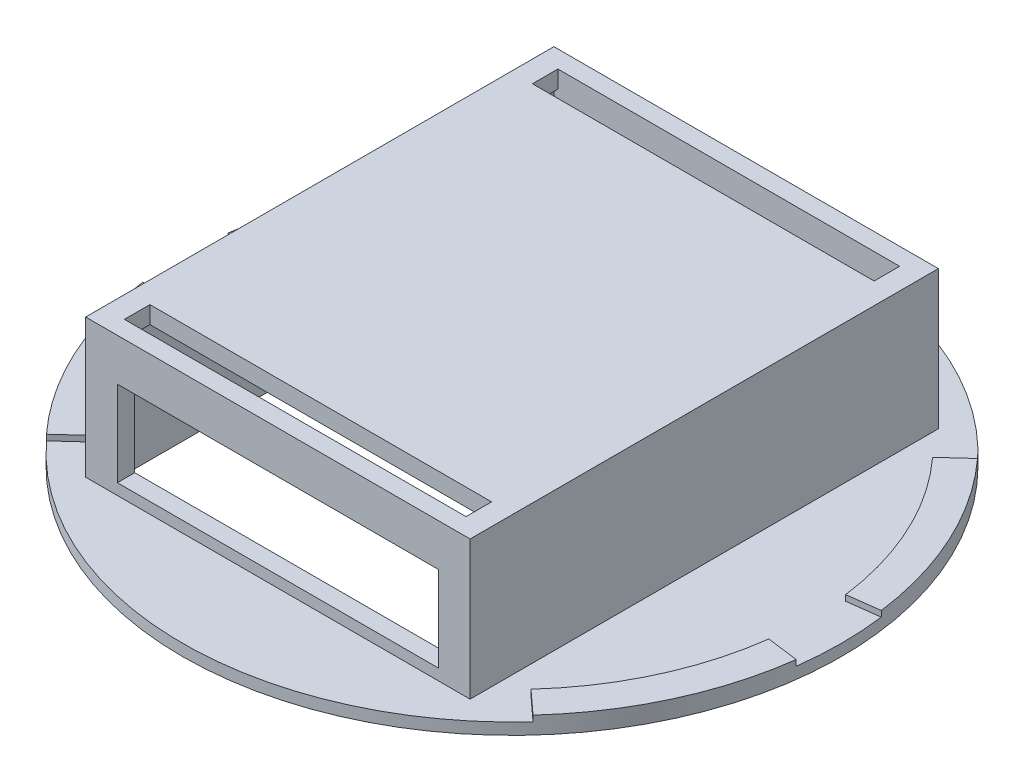
SolidWorks part; units mm, degrees
ref_plane "Front Plane" through (0, 0, 0) normal (0, 0, 1) x (1, 0, 0)
ref_plane "Top Plane" through (0, 0, 0) normal (0, 1, 0) x (1, 0, 0)
ref_plane "Right Plane" through (0, 0, 0) normal (1, 0, 0) x (0, 0, -1)
sketch "Sketch1" plane through (0, 0, 0) normal (0, 1, 0) x (1, 0, 0)
  line L0 (-72.3216, 0) -> (75.0576, 0) construction
  line L1 (0, 62.472) -> (0, -62.6544) construction
  line L2 (-56.5235, 7.3548) -> (-51.0695, 6.6452)
  line L3 (-42.0828, 38.4453) -> (-38.0222, 34.7356)
  line L4 (56.5235, 7.3548) -> (51.0695, 6.6452)
  line L5 (42.0828, 38.4453) -> (38.0222, 34.7356)
  line L6 (56.5235, -7.3548) -> (51.0695, -6.6452)
  line L7 (42.0828, -38.4453) -> (38.0222, -34.7356)
  line L8 (-56.5235, -7.3548) -> (-51.0695, -6.6452)
  line L9 (-42.0828, -38.4453) -> (-38.0222, -34.7356)
  circle A0 centre (0, 0) radius 57
  arc A1 (-38.0222, 34.7356) -> (-51.0695, 6.6452) centre (0, 0) ccw
  arc A2 (38.0222, 34.7356) -> (51.0695, 6.6452) centre (0, 0) cw
  arc A3 (38.0222, -34.7356) -> (51.0695, -6.6452) centre (0, 0) ccw
  arc A4 (-38.0222, -34.7356) -> (-51.0695, -6.6452) centre (0, 0) cw
  point P12 (-53.7965, 7)
  dimension "D1" = 114
  dimension "D2" = 103
  dimension "D3" = 35
  dimension "D4" = 7
extrude "Boss-Extrude1" add sketch "Sketch1" along normal blind 2 contours A4 L9 A0 L7 A3 L6 L4 A2 L5 L3 A1 L2 L8 | L5 A2 L4 A0 | A3 L7 A0 L6 | L9 A4 L8 A0 | A1 L3 A0 L2 region at (-48.4817, 0, -22.5185) region at (0, 0, 0) region at (-48.4817, 0, 22.5185) region at (48.4817, 0, -22.5185) region at (48.4817, 0, 22.5185)
extrude "Boss-Extrude3" add sketch "Sketch1<4>" along normal blind 3 contours A1 L3 A0 L2 | L9 A4 L8 A0 | A3 L7 A0 L6 | L5 A2 L4 A0 region at (-48.4817, 0, -22.5185) region at (-48.4817, 0, 22.5185) region at (48.4817, 0, -22.5185) region at (48.4817, 0, 22.5185)
sketch "Sketch1<4>" plane through (0, 0, 0) normal (0, 1, 0) x (1, 0, 0) same geometry as "Sketch1"
sketch "Sketch2" plane through (0, 2, 0) normal (0, 1, 0) x (1, 0, 0)
  line L0 (0, 66.6232) -> (0, -76.5642) construction
  line L1 (-80.9611, 0) -> (74.0789, 0) construction
  line L3 (-33.25, 40.5) -> (33.25, 40.5)
  line L4 (-33.25, 40.5) -> (-33.25, -40.5)
  line L5 (-33.25, -40.5) -> (33.25, -40.5)
  line L6 (33.25, 40.5) -> (33.25, -40.5)
  line L7 (-33.25, 40.5) -> (33.25, -40.5) construction
  line L8 (-33.25, -40.5) -> (33.25, 40.5) construction
  point P5 (0, 0)
  dimension "D1" = 81
  dimension "D2" = 66.5
extrude "Cut-Extrude1" cut sketch "Sketch2" against normal blind 3
extrude "Boss-Extrude4" add sketch "Sketch2<2>" along normal blind 24 separate body
sketch "Sketch2<2>" plane through (0, 2, 0) normal (0, 1, 0) x (1, 0, 0) same geometry as "Sketch2"
shell "Shell1" thickness 3 removed face at (0, 2, 0)
sketch "Sketch3" plane through (0, 0, -40.5) normal (0, 0, -1) x (-1, 0, 0)
  line L1 (-27.7597, 18.6939) -> (27.7597, 18.6939)
  line L2 (-27.7597, 18.6939) -> (-27.7597, 3.9216)
  line L3 (-27.7597, 3.9216) -> (27.7597, 3.9216)
  line L4 (27.7597, 18.6939) -> (27.7597, 3.9216)
  line L5 (-27.7597, 18.6939) -> (27.7597, 3.9216) construction
  line L6 (-27.7597, 3.9216) -> (27.7597, 18.6939) construction
  point P0 (0, 11.3078)
extrude "Cut-Extrude2" cut sketch "Sketch3" against normal blind 8
mirror "Mirror1" about plane through (0, 0, 0) normal (0, 0, 1) of "Cut-Extrude2"
sketch "Sketch4" plane through (0, 26, 0) normal (0, 1, 0) x (1, 0, 0)
  line L0 (-71.4503, 0) -> (0, 0) construction
  line L1 (0, 54.8821) -> (0, -41.5) construction
  line L2 (-29.5519, -33.0835) -> (29.5519, -33.0835)
  line L3 (-29.5519, 37.5) -> (29.5519, 37.5)
  line L12 (-29.5519, 37.5) -> (-29.5519, 33.0835)
  line L13 (-29.5519, 33.0835) -> (29.5519, 33.0835)
  line L14 (29.5519, 37.5) -> (29.5519, 33.0835)
  line L15 (-29.5519, 37.5) -> (29.5519, 33.0835) construction
  line L16 (-29.5519, 33.0835) -> (29.5519, 37.5) construction
  line L17 (29.5519, -37.5) -> (29.5519, -33.0835)
  line L18 (-29.5519, -37.5) -> (29.5519, -37.5)
  line L19 (-29.5519, -37.5) -> (-29.5519, -33.0835)
  line L20 (32.5, 0) -> (75.2737, 0) construction
  line L21 (33.25, 40.5) -> (-33.25, 40.5) construction
  point P9 (0, 35.2917)
  dimension "D1" = 3
extrude "Cut-Extrude5" cut sketch "Sketch4" against normal blind 8
sketch "Sketch5" plane through (0, 0, 0) normal (0, -1, 0) x (1, 0, 0)
  line L0 (-69.3793, 0) -> (71.291, 0) construction
  line L1 (0, 64.8071) -> (0, -66.6424) construction
  line L2 (-46.2253, 11.5807) -> (-46.2253, -12.4673) construction
  line L3 (-48.4753, 5) -> (-43.9753, 5)
  line L4 (-48.4753, 5) -> (-48.4753, -5)
  line L5 (-48.4753, -5) -> (-43.9753, -5)
  line L6 (-43.9753, 5) -> (-43.9753, -5)
  line L7 (-48.4753, 5) -> (-43.9753, -5) construction
  line L8 (-48.4753, -5) -> (-43.9753, 5) construction
  circle A0 centre (-46.2253, 7) radius 1
  circle A1 centre (-46.2253, -7) radius 1
  point P5 (-46.2253, 0)
  dimension "D3" = 2
  dimension "D1" = 10
  dimension "D2" = 4.5
  dimension "D4" = 2
extrude "Cut-Extrude6" cut sketch "Sketch5" against normal blind 8
